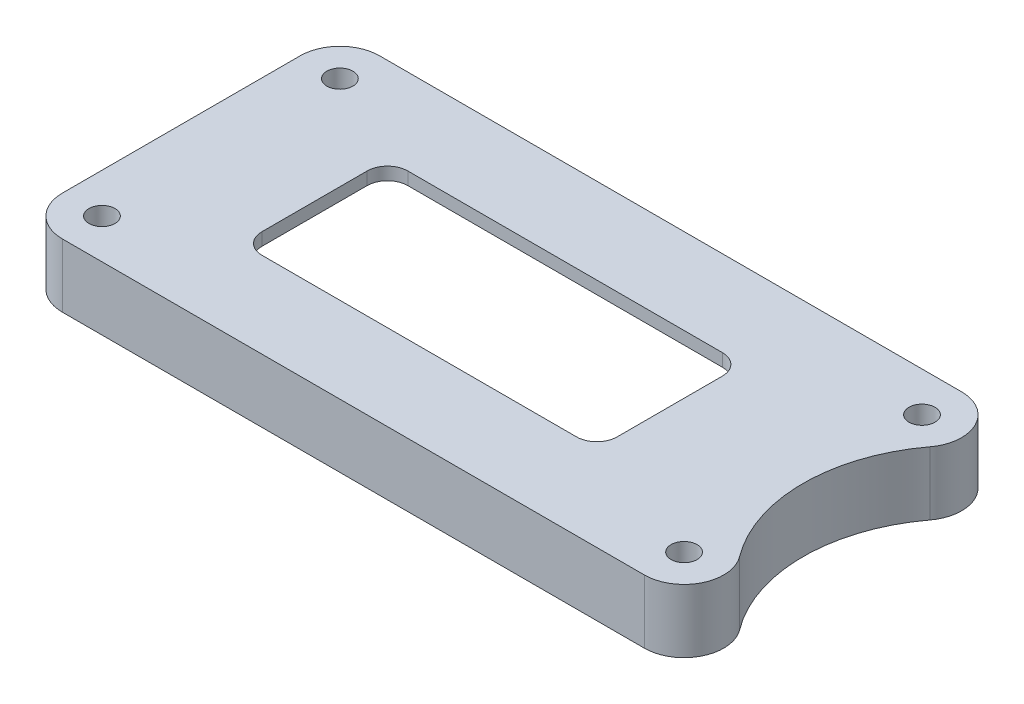
SolidWorks part; units mm, degrees
ref_plane "Front Plane" through (0, 0, 0) normal (0, 0, 1) x (1, 0, 0)
ref_plane "Top Plane" through (0, 0, 0) normal (0, 1, 0) x (1, 0, 0)
ref_plane "Right Plane" through (0, 0, 0) normal (1, 0, 0) x (0, 0, -1)
sketch "Sketch1" plane through (0, 0, 0) normal (0, 1, 0) x (1, 0, 0)
  line L1 (-22.5, 12.5) -> (22.5, 12.5)
  line L2 (-22.5, 12.5) -> (-22.5, -12.5)
  line L3 (-22.5, -12.5) -> (22.5, -12.5)
  line L4 (22.5, 12.5) -> (22.5, -12.5)
  line L5 (-22.5, 12.5) -> (22.5, -12.5) construction
  line L6 (-22.5, -12.5) -> (22.5, 12.5) construction
  point P0 (0, 0)
  dimension "D1" = 25
  dimension "D2" = 45
extrude "Boss-Extrude1" add sketch "Sketch1" along normal blind 5
sketch "Sketch2" plane through (0, 5, 0) normal (0, 1, 0) x (1, 0, 0)
  line L1 (-14, -5.75) -> (14, -5.75)
  line L2 (-14, -5.75) -> (-14, 5.75)
  line L3 (-14, 5.75) -> (14, 5.75)
  line L4 (14, -5.75) -> (14, 5.75)
  line L5 (-14, -5.75) -> (14, 5.75) construction
  line L6 (-14, 5.75) -> (14, -5.75) construction
  point P0 (0, 0)
  dimension "D1" = 28
  dimension "D2" = 11.5
extrude "Cut-Extrude1" cut sketch "Sketch2" against normal through all
shell "Shell1" thickness 1 removed face at (14, 2.5, 0) removed face at (0, 2.5, 5.75) removed face at (-14, 2.5, 0) removed face at (0, 2.5, -5.75) removed face at (0, 0, 0)
fillet "Fillet1" radius 1.6 4 edges at (-14, 4.5, -5.75) (14, 4.5, -5.75) (14, 4.5, 5.75) (-14, 4.5, 5.75)
sketch "Sketch3" plane through (0, 4, 0) normal (0, -1, 0) x (1, 0, 0)
  line L4 (21.5, -11.5) -> (21.5, 11.5)
  line L5 (21.5, 11.5) -> (-21.5, 11.5)
  line L6 (-21.5, 11.5) -> (-21.5, -11.5)
  line L7 (-21.5, -11.5) -> (21.5, -11.5)
  line L8 (21.5, -11.5) -> (21.5, 11.5)
  line L9 (21.5, 11.5) -> (-21.5, 11.5)
  line L10 (-21.5, 11.5) -> (-21.5, -11.5)
  line L11 (-21.5, -11.5) -> (21.5, -11.5)
  circle A0 centre (-12.9353, 8.721) radius 1.25 construction
  circle A1 centre (17.0647, 8.721) radius 1.25 construction
  circle A2 centre (17.0647, -7.779) radius 1.25 construction
  circle A3 centre (-12.9353, -7.779) radius 1.25 construction
  circle A4 centre (-12.9353, 8.721) radius 1.25
  circle A5 centre (17.0647, 8.721) radius 1.25
  circle A6 centre (17.0647, -7.779) radius 1.25
  circle A7 centre (-12.9353, -7.779) radius 1.25
  dimension "D1" = 0
fillet "Fillet2" radius 3.125 4 edges at (-21.5, 2, 11.5) (-21.5, 2, -11.5) (21.5, 2, 11.5) (21.5, 2, -11.5)
sketch "Sketch4" plane through (0, 0, 0) normal (0, -1, 0) x (1, 0, 0)
  line L0 (22.5, -12.5) -> (37, -12.5)
  line L1 (22.5, 12.5) -> (40, 12.5)
  line L2 (-22.5, -12.5) -> (-27.5, -12.5)
  line L3 (-22.5, 12.5) -> (-27.5, 12.5)
  line L4 (22.5, -12.5) -> (22.5, 12.5)
  line L5 (22.5, 12.5) -> (-22.5, 12.5)
  line L6 (-22.5, 12.5) -> (-22.5, -12.5)
  line L7 (-22.5, -12.5) -> (22.5, -12.5)
  line L8 (22.5, -12.5) -> (22.5, 12.5)
  line L9 (22.5, 12.5) -> (-22.5, 12.5)
  line L10 (-22.5, 12.5) -> (-22.5, -12.5)
  line L11 (-22.5, -12.5) -> (22.5, -12.5)
  circle A0 centre (37, 0) radius 12.5
  circle A1 centre (-27.5, 0) radius 12.5
  line M15 (22.5, -12.5) -> (22.5, 12.5)
  dimension "D2" = 25
  dimension "D4" = 25
  dimension "D3" = 14.5
  dimension "D5" = 5
  dimension "D1" = 0
extrude "Boss-Extrude2" add sketch "Sketch4" against normal up to surface (5 mm away) contours A0 L1 L0 M15 region at (22.789, 0, 0) up to face at (0, 5, 0)
fillet "Fillet3" radius 3.125 2 edges at (37, 2.5, -12.5) (37, 2.5, 12.5)
fillet "Fillet4" radius 3.125 2 edges at (-22.5, 2.5, -12.5) (-22.5, 2.5, 12.5)
sketch "Sketch6" plane through (0, 0, 0) normal (0, -1, 0) x (1, 0, 0)
  line L1 (-22.5, -12.5) -> (-24.5, -12.5)
  line L2 (-22.5, -12.5) -> (-22.5, 12.5)
  line L3 (-22.5, 9.375) -> (-22.5, -9.375)
  line L4 (-19.375, -12.5) -> (24.5, -12.5)
  line L5 (24.5, 12.5) -> (-19.375, 12.5)
  line L6 (-22.5, 9.375) -> (-22.5, -9.375)
  line L7 (-19.375, -12.5) -> (24.5, -12.5)
  line L8 (24.5, 12.5) -> (-19.375, 12.5)
  line L9 (-22.5, 12.5) -> (-24.5, 12.5)
  line L10 (-22.5, -12.5) -> (22.5, -12.5)
  line L11 (22.5, -12.5) -> (22.5, 12.5)
  line L12 (22.5, 12.5) -> (-22.5, 12.5)
  line L13 (-22.5, 12.5) -> (-22.5, -12.5)
  line L14 (-22.5, -12.5) -> (22.5, -12.5)
  line L15 (22.5, -12.5) -> (22.5, 12.5)
  line L16 (22.5, 12.5) -> (-22.5, 12.5)
  line L17 (-22.5, 12.5) -> (-22.5, -12.5)
  line L18 (-24.5, -12.5) -> (-24.5, 12.5)
  line L19 (-22.5, -12.5) -> (-18.375, -12.5)
  line L20 (-22.5, -12.5) -> (-22.5, 12.5)
  line L21 (-22.5, 12.5) -> (-18.375, 12.5)
  line L22 (-18.375, -12.5) -> (-18.375, 12.5)
  arc A6 (-22.5, -9.375) -> (-19.375, -12.5) centre (-19.375, -9.375) ccw
  arc A7 (24.5, -12.5) -> (27, -7.5) centre (24.5, -9.375) ccw
  arc A8 (27, 7.5) -> (27, -7.5) centre (37, 0) ccw
  arc A9 (27, 7.5) -> (24.5, 12.5) centre (24.5, 9.375) ccw
  arc A10 (-19.375, 12.5) -> (-22.5, 9.375) centre (-19.375, 9.375) ccw
  arc A11 (-22.5, -9.375) -> (-19.375, -12.5) centre (-19.375, -9.375) ccw
  arc A12 (24.5, -12.5) -> (27, -7.5) centre (24.5, -9.375) ccw
  arc A13 (27, 7.5) -> (27, -7.5) centre (37, 0) ccw
  arc A14 (27, 7.5) -> (24.5, 12.5) centre (24.5, 9.375) ccw
  arc A15 (-19.375, 12.5) -> (-22.5, 9.375) centre (-19.375, 9.375) ccw
  line M15 (-21.5, -8.375) -> (-21.5, 8.375)
  arc M16 (-21.5, 8.375) -> (-18.375, 11.5) centre (-18.375, 8.375) cw
  arc M22 (-18.375, -11.5) -> (-21.5, -8.375) centre (-18.375, -8.375) cw
  line M23 (-22.5, 9.375) -> (-22.5, -9.375)
  arc M24 (-22.5, -9.375) -> (-19.375, -12.5) centre (-19.375, -9.375) ccw
  line M25 (-19.375, -12.5) -> (24.5, -12.5)
  arc M30 (-19.375, 12.5) -> (-22.5, 9.375) centre (-19.375, 9.375) ccw
  dimension "D3" = 2
  dimension "D1" = 0
  dimension "D2" = 0
extrude "Boss-Extrude3" add sketch "Sketch6" against normal up to surface (5 mm away) contours L22 M22 M16 M15 | L18 L1 L2 L9 M23 | L22 L16 M25 M22 M15 M16 M30 M23 M24 | L2 L14 M24 | L16 L2 M30 region at (-23.5, 0, 0) region at (-21.802, 0, -11.802) region at (-22.2466, 0, 0) region at (-21.802, 0, 11.802) region at (-19.884, 0, 0) up to face at (0, 5, 0)
fillet "Fillet5" radius 3.125 4 edges at (-24.5, 2.5, -12.5) (-24.5, 2.5, 12.5) (-18.375, 2, 11.5) (-18.375, 2, -11.5)
sketch "Sketch7" plane through (0, 0, 0) normal (0, -1, 0) x (-1, 0, 0)
  line L0 (-2.75, 0) -> (2.75, 0) construction
  circle A0 centre (-24.5, 9.375) radius 1.025
  circle A1 centre (-24.5, -9.375) radius 1.025
  circle A2 centre (21.375, 9.375) radius 1.025
  circle A3 centre (21.375, -9.375) radius 1.025
  dimension "D1" = 2.05
  dimension "D2" = 2.05
extrude "Cut-Extrude2" cut sketch "Sketch7" against normal through all contours A0 | A1 | A3 | A2 region at (24.5, 0, -9.375) region at (24.5, 0, 9.375) region at (-21.375, 0, -9.375) region at (-21.375, 0, 9.375)
